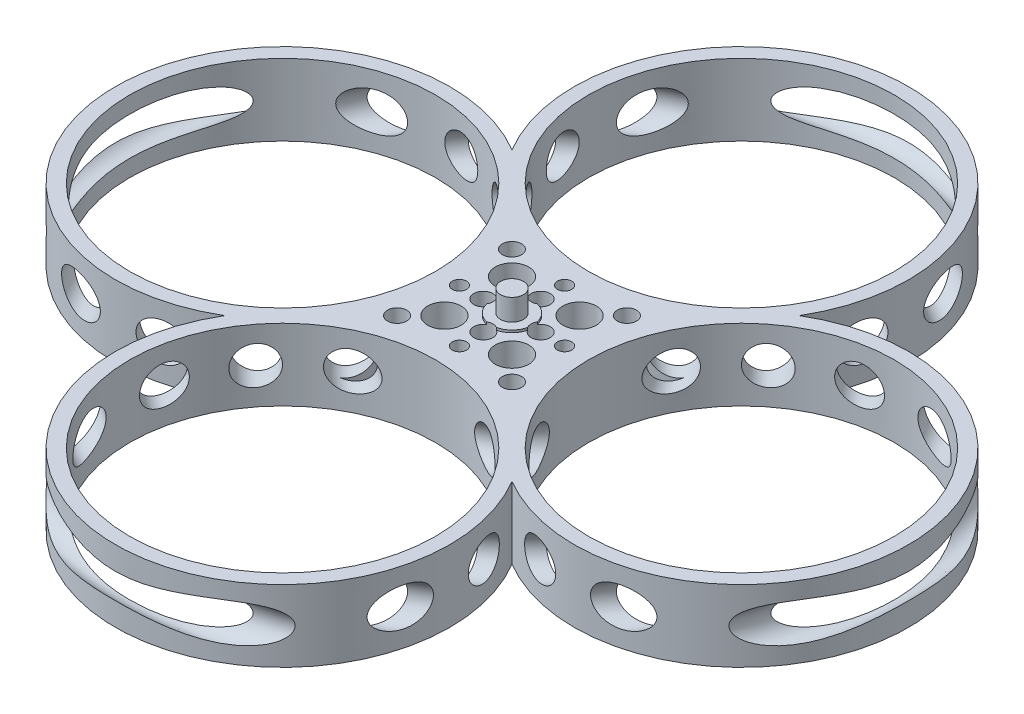
SolidWorks part; units mm, degrees
ref_plane "Ön Düzlem" through (0, 0, 0) normal (0, 0, 1) x (1, 0, 0)
ref_plane "Üst Düzlem" through (0, 0, 0) normal (0, 1, 0) x (1, 0, 0)
ref_plane "Sağ Düzlem" through (0, 0, 0) normal (1, 0, 0) x (0, 0, -1)
sketch "Çizim1" plane through (0, 0, 0) normal (0, 1, 0) x (1, 0, 0)
  circle A0 centre (0, 48) radius 32
  circle A1 centre (48, 0) radius 32
  circle A2 centre (-48, 0) radius 32
  circle A3 centre (0, -48) radius 32
  dimension "D1" = 64
  dimension "D2" = 48
  dimension "D3" = 48
  dimension "D4" = 48
  dimension "D5" = 48
extrude "Ekstrüzyon-İnce2" add sketch "Çizim1" along normal blind 15 thin thin type one direction wall 3
sketch "Çizim2" plane through (0, 15, 0) normal (0, 1, 0) x (1, 0, 0)
  circle A0 centre (0, 48) radius 35 construction
  circle A1 centre (-48, 0) radius 35
  arc A2 (-17.9585, -17.9585) -> (-17.9585, 17.9585) centre (-48, 0) ccw
  circle A3 centre (48, 0) radius 35 construction
  circle A4 centre (0, -48) radius 35 construction
  arc A5 (17.9585, -17.9585) -> (-17.9585, -17.9585) centre (0, -48) ccw
  arc A6 (17.9585, 17.9585) -> (17.9585, -17.9585) centre (48, 0) ccw
  arc A7 (-17.9585, 17.9585) -> (17.9585, 17.9585) centre (0, 48) ccw
  dimension "D1" = 0
extrude "Yükseklik-Ekstrüzyon1" add sketch "Çizim2" against normal blind 5
sketch "Çizim3" plane through (0, 15, 0) normal (0, 1, 0) x (1, 0, 0)
  circle A0 centre (0, 0) radius 2.4
  circle A1 centre (0, 0) radius 4.4
  dimension "D1" = 4.8
  dimension "D2" = 2
extrude "Yükseklik-Ekstrüzyon2" add sketch "Çizim3" along normal blind 5 contours A0
extrude "Yükseklik-Ekstrüzyon3" add sketch "Çizim3<3>" along normal blind 0.5
sketch "Çizim3<3>" plane through (0, 15, 0) normal (0, 1, 0) x (1, 0, 0) same geometry as "Çizim3"
sketch "Çizim6" plane through (0, 10, 0) normal (0, -1, 0) x (1, 0, 0)
  line L0 (-17.9585, 17.9585) -> (17.9585, -17.9585) construction
  line L1 (17.9585, 17.9585) -> (-17.9585, -17.9585) construction
  circle A0 centre (7.0711, 7.0711) radius 3.5
  circle A1 centre (12.0208, 12.0208) radius 2
  circle A2 centre (0, 6) radius 2
  circle A3 centre (0, 11) radius 1.5
  dimension "D2" = 7
  dimension "D4" = 4
  dimension "D5" = 4
  dimension "D6" = 3
  dimension "D1" = 10
  dimension "D3" = 7
  dimension "D7" = 5
  dimension "D8" = 6
extrude "Kes-Ekstrüzyon2" cut sketch "Çizim6" against normal through all
pattern_circular "Dairesel Kaplama1" count 4 over 360 about axis through (0, 20, 0) along (0, -1, 0) of "Kes-Ekstrüzyon2" reverse direction yes
sketch "Çizim7" plane through (0, 10, 0) normal (0, -1, 0) x (1, 0, 0)
  circle A2 centre (0, 0) radius 2.5
  circle A3 centre (0, 0) radius 3.5
  dimension "D1" = 5
  dimension "D2" = 1
extrude "Yükseklik-Ekstrüzyon4" add sketch "Çizim7" along normal blind 6
extrude "Kes-Ekstrüzyon3" cut sketch "Çizim7<2>" against normal blind 3 contours A2 region at (0, 10, 0)
sketch "Çizim7<2>" plane through (0, 10, 0) normal (0, -1, 0) x (1, 0, 0) same geometry as "Çizim7"
sketch "Sketch2" plane through (0, 0, 0) normal (1, 0, 0) x (0, 0, -1)
  line L0 (-89.018, 7.5) -> (-10.2754, 7.5) construction
  line L1 (-16, 19.611) -> (-16, -3.0235) construction
  line L2 (0, 0) -> (0, 31.5689) construction
  circle A0 centre (-24, 7.5) radius 4
  circle A5 centre (-38, 7.5) radius 4
  circle A6 centre (-52, 7.5) radius 4
  circle A7 centre (-66, 7.5) radius 4
  circle A8 centre (-80, 7.5) radius 4
  dimension "D2" = 8
  dimension "D3" = 5
  dimension "D1" = 7.5
  dimension "D4" = 16
  dimension "D5" = 8
revolve "Cut-Revolve1" cut sketch "Sketch2" angle 360 about L2
equation "\"D4@Çizim1\"=\"D5@Çizim1\""
equation "\"D3@Çizim1\"=\"D5@Çizim1\""
equation "\"D2@Çizim1\"=\"D5@Çizim1\""
